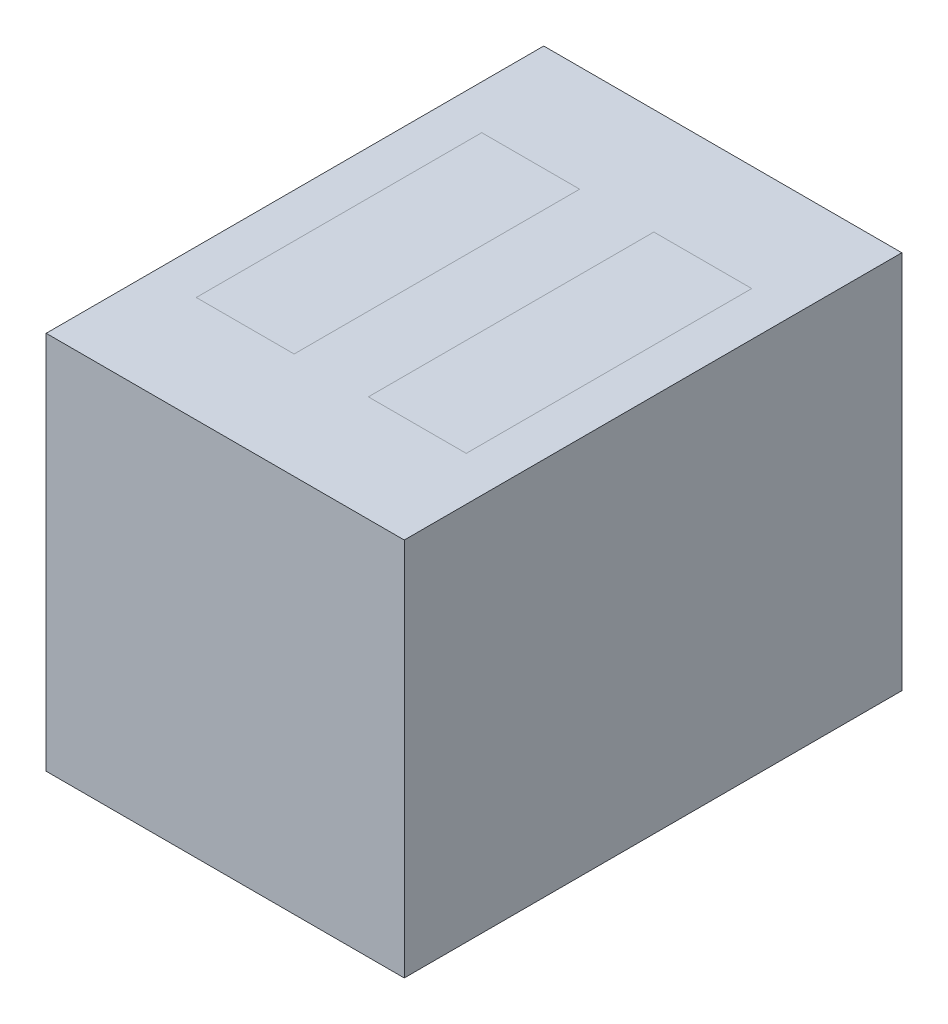
SolidWorks part; units mm, degrees
other "Light"
other "Sensor"
other "Body"
ref_plane "Front Plane" through (0, 0, 0) normal (0, 0, 1) x (1, 0, 0)
ref_plane "Top Plane" through (0, 0, 0) normal (0, 1, 0) x (1, 0, 0)
ref_plane "Right Plane" through (0, 0, 0) normal (1, 0, 0) x (0, 0, -1)
sketch "Sketch1" plane through (0, 0, 0) normal (0, 1, 0) x (1, 0, 0)
  line L1 (0, 0) -> (4.39, 0)
  line L2 (0, 0) -> (0, 6.1)
  line L3 (0, 6.1) -> (4.39, 6.1)
  line L4 (4.39, 0) -> (4.39, 6.1)
  dimension "D1" = 4.39
  dimension "D2" = 6.1
extrude "Boss-Extrude1" add sketch "Sketch1" along normal blind 4.65
sketch "Sketch2" plane through (0, 4.65, 0) normal (0, 1, 0) x (1, 0, 0)
  line L0 (2.195, 6.1) -> (2.195, 0) construction
  line L1 (0.54, 4.8) -> (1.74, 4.8)
  line L2 (0.54, 4.8) -> (0.54, 1.3)
  line L3 (0.54, 1.3) -> (1.74, 1.3)
  line L4 (1.74, 4.8) -> (1.74, 1.3)
  line L5 (4.39, 6.1) -> (0, 6.1) construction
  line L6 (0, 0) -> (4.39, 0) construction
  line L8 (1.14, 4.8) -> (1.14, 1.3) construction
  line L9 (0.54, 3.05) -> (1.74, 3.05) construction
  line L10 (0, 6.1) -> (0, 0) construction
  line L11 (3.85, 3.05) -> (2.65, 3.05) construction
  line L12 (3.25, 4.8) -> (3.25, 1.3) construction
  line L13 (2.65, 4.8) -> (2.65, 1.3)
  line L14 (3.85, 1.3) -> (2.65, 1.3)
  line L15 (3.85, 4.8) -> (3.85, 1.3)
  line L16 (3.85, 4.8) -> (2.65, 4.8)
  dimension "D1" = 1.14
  dimension "D2" = 3.05
  dimension "D3" = 3.5
  dimension "D4" = 1.2
extrude "Cut-Extrude1" cut sketch "Sketch2" against normal blind 2
extrude "Boss-Extrude2" add sketch "Sketch2<3>" against normal up to surface (2 mm away) separate body up to face at (3.25, 2.65, -3.05)
sketch "Sketch2<3>" plane through (0, 4.65, 0) normal (0, 1, 0) x (1, 0, 0) same geometry as "Sketch2"
